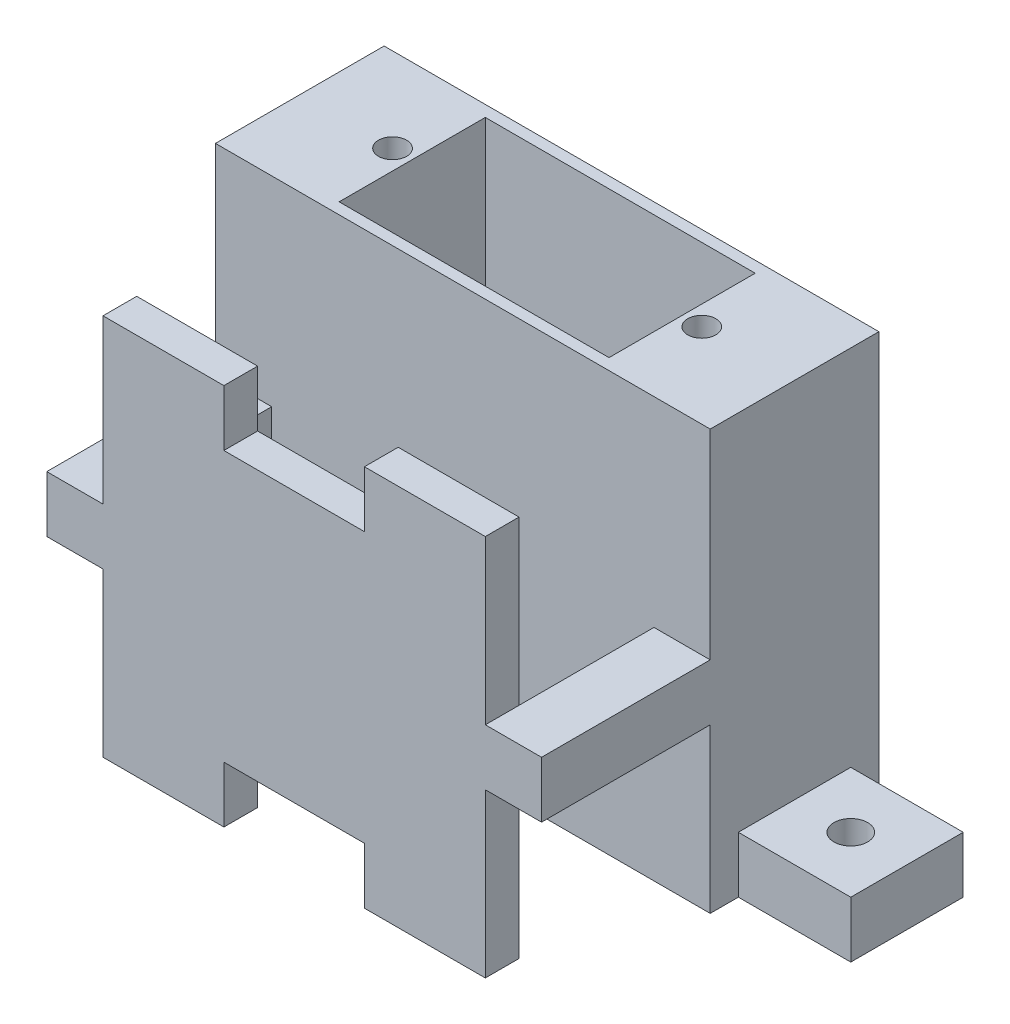
SolidWorks part; units mm, degrees
ref_plane "Front Plane" through (0, 0, 0) normal (0, 0, 1) x (1, 0, 0)
ref_plane "Top Plane" through (0, 0, 0) normal (0, 1, 0) x (1, 0, 0)
ref_plane "Right Plane" through (0, 0, 0) normal (1, 0, 0) x (0, 0, -1)
sketch "Sketch1" plane through (0, 0, 0) normal (0, 0, 1) x (1, 0, 0)
  line L0 (0, 0) -> (0, -34)
  line L1 (0, -34) -> (34, -34)
  line L2 (34, -34) -> (34, 0)
  line L3 (34, 0) -> (0, 0)
  dimension "D1" = 34
  dimension "D2" = 34
extrude "Boss-Extrude1" add sketch "Sketch1" along normal blind 3
sketch "Sketch2" plane through (0, 0, 0) normal (0, 0, -1) x (-1, 0, 0)
  line L0 (-17, 0) -> (-17, -34) construction
  line L1 (-34, 0) -> (0, 0) construction
  line L2 (0, -34) -> (-34, -34) construction
  line L3 (-34, -17) -> (0, -17) construction
  line L4 (-34, -34) -> (-34, 0) construction
  line L5 (0, 0) -> (0, -34) construction
  line L6 (-23.25, -5) -> (-10.75, -5)
  line L7 (-10.75, -5) -> (-10.75, 0)
  line L8 (-10.75, 0) -> (-23.25, 0)
  line L9 (-23.25, -5) -> (-23.25, 0)
  line L10 (-10.75, -29) -> (-10.75, -34)
  line L11 (-23.25, -29) -> (-10.75, -29)
  line L12 (-23.25, -29) -> (-23.25, -34)
  line L13 (-10.75, -34) -> (-23.25, -34)
  point P17 (-17, -5)
  dimension "D1" = 6.25
  dimension "D2" = 5
extrude "Cut-Extrude1" cut sketch "Sketch2" against normal through all contours L8 L9 L6 L7 | L10 L13 L12 L11
sketch "Sketch25" plane through (34, 0, 0) normal (1, 0, 0) x (0, 0, -1)
  line L0 (-3, -17) -> (0, -17) construction
  line L1 (-3, -34) -> (-3, 0) construction
  line L2 (0, -34) -> (0, 0) construction
  line L3 (-3, -17) -> (-3, -14.5)
  line L4 (-3, -14.5) -> (12, -14.5)
  line L11 (12, -14.5) -> (12, -19.5)
  line L12 (-3, -17) -> (-3, -19.5)
  line L13 (-3, -19.5) -> (12, -19.5)
  dimension "D1" = 2.5
  dimension "D2" = 15
  dimension "D4" = 5
extrude "Boss-Extrude2" add sketch "Sketch25" along normal blind 5
sketch "Sketch31" plane through (0, 0, 0) normal (0, 0, -1) x (-1, 0, 0)
  line L0 (-17, -5) -> (-17, -29) construction
  line L1 (-23.25, -5) -> (-10.75, -5) construction
  line L2 (-23.25, -29) -> (-10.75, -29) construction
sketch "Sketch33" plane through (0, 0, 0) normal (-1, 0, 0) x (0, 0, 1)
  line L0 (3, -14.5) -> (-12, -14.5)
  line L1 (-12, -14.5) -> (-12, -19.5)
  line L2 (-12, -19.5) -> (3, -19.5)
  line L3 (3, -19.5) -> (3, -14.5)
  dimension "D1" = 15
extrude "Boss-Extrude4" add sketch "Sketch33" along normal blind 5
sketch "Sketch35" plane through (0, 0, -12) normal (0, 0, -1) x (-1, 0, 0)
  line L6 (-39, -17) -> (-39, 3.2777)
  line L7 (-39, -19.5) -> (-39, -14.5) construction
  line L8 (-39, 3.2777) -> (5, 3.2777)
  line L9 (5, 3.2777) -> (5, -17)
  line L10 (5, -14.5) -> (5, -19.5) construction
  line L11 (5, -17) -> (5, -34.026)
  line L12 (5, -34.026) -> (-39, -34.026)
  line L13 (-39, -34.026) -> (-39, -17)
  dimension "D1" = 44
  dimension "D2" = 44
  dimension "D3" = 37.3037
extrude "Boss-Extrude6" add sketch "Sketch35" along normal blind 15
sketch "Sketch36" plane through (0, 3.2777, 0) normal (0, 1, 0) x (1, 0, 0)
  line L0 (17, 27) -> (17, 12) construction
  line L1 (-5, 27) -> (39, 27) construction
  line L2 (-5, 12) -> (39, 12) construction
  line L3 (5, 26) -> (29, 26)
  line L4 (29, 26) -> (29, 13)
  line L5 (29, 13) -> (5, 13)
  line L6 (5, 26) -> (5, 13)
  point P11 (17, 13)
  point P12 (17, 26)
  dimension "D1" = 12
  dimension "D2" = 13
  dimension "D3" = 1
extrude "Cut-Extrude2" cut sketch "Sketch36" against normal blind 19.5
sketch "Sketch38" plane through (0, -34.026, 0) normal (0, -1, 0) x (-1, 0, 0)
  line L0 (-39, 19.5) -> (5, 19.5) construction
  line L1 (-39, 27) -> (-39, 12) construction
  line L2 (5, 27) -> (5, 12) construction
  line L3 (-39, 24.5) -> (-39, 14.5)
  line L4 (-39, 14.5) -> (-49, 14.5)
  line L5 (-49, 14.5) -> (-49, 17)
  line L6 (-39, 24.5) -> (-49, 24.5)
  line L7 (-49, 24.5) -> (-49, 22)
  line L8 (-17, 12) -> (-17, 27) construction
  line L9 (-39, 12) -> (5, 12) construction
  line L10 (-39, 27) -> (5, 27) construction
  line L11 (5, 24.5) -> (5, 14.5)
  line L12 (5, 24.5) -> (15, 24.5)
  line L13 (15, 24.5) -> (15, 22)
  line L14 (15, 14.5) -> (15, 17)
  line L15 (5, 14.5) -> (15, 14.5)
  line L16 (-49, 22) -> (-49, 17)
  line L17 (15, 22) -> (15, 17)
  line M9 (5, 12) -> (5, 27)
  line M11 (-39, 27) -> (-39, 12)
  dimension "D1" = 10
  dimension "D2" = 2.5
extrude "Boss-Extrude7" add sketch "Sketch38" against normal blind 5 contours L15 L14 L13 L12 M9 | L6 L7 L5 L4 M11 region at (44, -34.026, -19.5) region at (-10, -34.026, -19.5)
sketch "Sketch39" plane through (0, -29.026, 0) normal (0, 1, 0) x (1, 0, 0)
  line L0 (-10, 24.5) -> (-10, 14.5) construction
  line L1 (-5, 24.5) -> (-15, 24.5) construction
  line L2 (-5, 14.5) -> (-15, 14.5) construction
  line L3 (44, 24.5) -> (44, 14.5) construction
  line L4 (39, 24.5) -> (49, 24.5) construction
  line L5 (39, 14.5) -> (49, 14.5) construction
  circle A0 centre (-10, 19.5) radius 1.5
  circle A1 centre (44, 19.5) radius 1.5
extrude "Cut-Extrude3" cut sketch "Sketch39" against normal through all
sketch "Sketch40" plane through (0, 3.2777, 0) normal (0, 1, 0) x (1, 0, 0)
  line L0 (-5, 19.5) -> (50.8322, 19.5) construction
  line L1 (-5, 14.5) -> (-5, 24.5) construction
  line L2 (17, 27) -> (17, 10.2754) construction
  line L3 (-5, 27) -> (39, 27) construction
  circle A0 centre (3.25, 19.5) radius 1.25
  circle A1 centre (30.75, 19.5) radius 1.25
  dimension "D1" = 2.5
  dimension "D2" = 27.5
extrude "Cut-Extrude4" cut sketch "Sketch40" against normal blind 5
